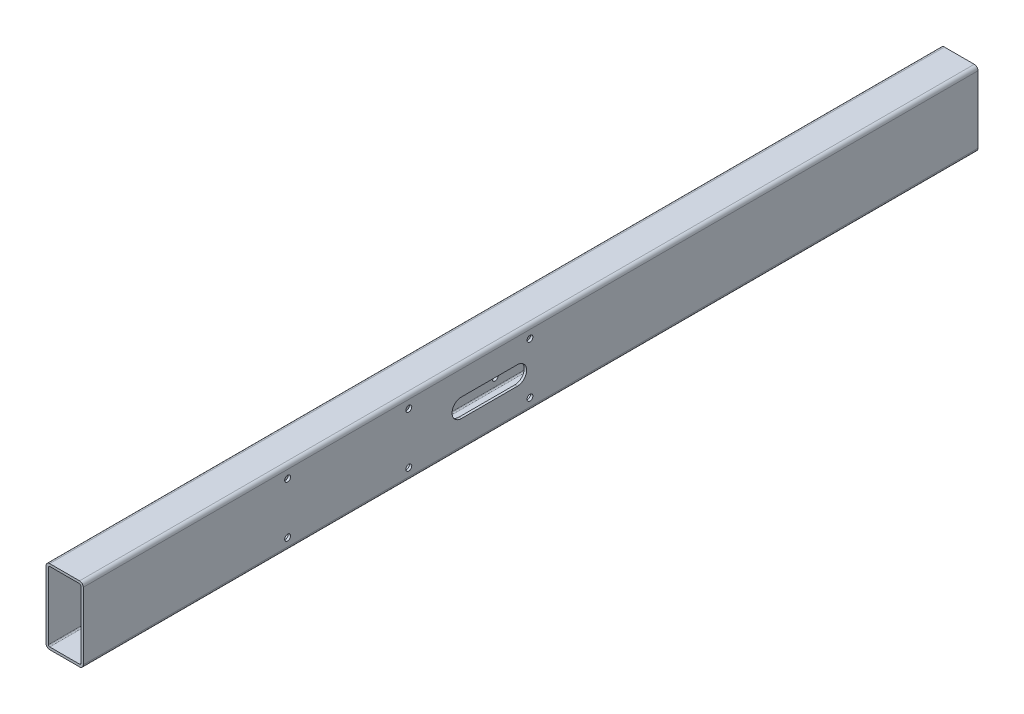
SolidWorks part; units mm, degrees
material "6061-T6 (SS)"
ref_plane "Front Plane" through (0, 0, 0) normal (0, 0, 1) x (1, 0, 0)
ref_plane "Top Plane" through (0, 0, 0) normal (0, 1, 0) x (1, 0, 0)
ref_plane "Right Plane" through (0, 0, 0) normal (1, 0, 0) x (0, 0, -1)
sketch "Sketch1" plane through (0, 0, 0) normal (0, 0, 1) x (1, 0, 0)
  line L1 (10.16, -25.4) -> (-10.16, -25.4)
  line L2 (12.7, -22.86) -> (12.7, 22.86)
  line L3 (10.16, 25.4) -> (-10.16, 25.4)
  line L4 (-12.7, -22.86) -> (-12.7, 22.86)
  line L5 (12.7, -25.4) -> (-12.7, 25.4) construction
  line L6 (12.7, 25.4) -> (-12.7, -25.4) construction
  arc A0 (-10.16, -25.4) -> (-12.7, -22.86) centre (-10.16, -22.86) cw
  arc A1 (10.16, -25.4) -> (12.7, -22.86) centre (10.16, -22.86) ccw
  arc A2 (12.7, 22.86) -> (10.16, 25.4) centre (10.16, 22.86) ccw
  arc A3 (-10.16, 25.4) -> (-12.7, 22.86) centre (-10.16, 22.86) ccw
  point P0 (0, 0)
  dimension "D3" = 2.54
  dimension "D1" = 25.4
  dimension "D2" = 50.8
extrude "Extrude-Thin1" add sketch "Sketch1" along normal mid plane 609.6 thin thin type one direction reverse wall 1.651
sketch "Sketch3" plane through (-12.7, 0, 0) normal (-1, 0, 0) x (0, 0, 1)
  line L0 (156.936, 0) -> (9.0855, 0) construction
  line L1 (156.936, -2.5527) -> (9.0855, -2.5527)
  line L2 (156.936, 2.5527) -> (9.0855, 2.5527)
  line L4 (150.586, 0) -> (279.4, 276.2426) construction
  line L5 (279.4, 276.2426) -> (279.4, 152.4) construction
  line L6 (279.4, 152.4) -> (15.4355, 0) construction
  line L7 (304.8, -22.86) -> (304.8, 22.86) construction
  arc A0 (156.936, -2.5527) -> (156.936, 2.5527) centre (156.936, 0) ccw
  arc A1 (9.0855, 2.5527) -> (9.0855, -2.5527) centre (9.0855, 0) ccw
  point P3 (83.0107, 0)
  point P10 (-6.3242, 0)
  dimension "D1" = 5.1054
  dimension "D2" = 6.35
  dimension "D3" = 30
  dimension "D4" = 6.35
  dimension "D5" = 25.4
  dimension "D6" = 304.8
  dimension "D7" = 65
extrude "Cut-Extrude2" cut sketch "Sketch3" against normal up to next
sketch "Sketch6" plane through (12.7, 0, 0) normal (1, 0, 0) x (0, 0, -1)
  line L0 (-47.1855, 0) -> (-9.0855, 0) construction
  line L1 (-47.1855, 6.35) -> (-9.0855, 6.35)
  line L2 (-47.1855, -6.35) -> (-9.0855, -6.35)
  arc A0 (-47.1855, 6.35) -> (-47.1855, -6.35) centre (-47.1855, 0) ccw
  arc A1 (-9.0855, -6.35) -> (-9.0855, 6.35) centre (-9.0855, 0) ccw
  point P2 (-28.1355, 0)
  dimension "D1" = 6.35
  dimension "D2" = 38.1
extrude "Cut-Extrude4" cut sketch "Sketch6" against normal up to next
sketch "Sketch5" plane through (12.7, 0, 0) normal (1, 0, 0) x (0, 0, -1)
  circle A0 centre (-0.4607, 17.399) radius 2.0193 construction
  circle A1 centre (-0.4607, -17.399) radius 2.0193 construction
  circle A2 centre (-83.0107, 17.399) radius 2.0193 construction
  circle A3 centre (-83.0107, -17.399) radius 2.0193 construction
  circle A4 centre (-165.5607, -17.399) radius 2.0193 construction
  circle A5 centre (-165.5607, 17.399) radius 2.0193 construction
  circle A6 centre (-0.4607, 17.399) radius 2.0193
  circle A7 centre (-0.4607, -17.399) radius 2.0193
  circle A8 centre (-83.0107, 17.399) radius 2.0193
  circle A9 centre (-83.0107, -17.399) radius 2.0193
  circle A10 centre (-165.5607, -17.399) radius 2.0193
  circle A11 centre (-165.5607, 17.399) radius 2.0193
extrude "Cut-Extrude3" cut sketch "Sketch5" against normal through all
